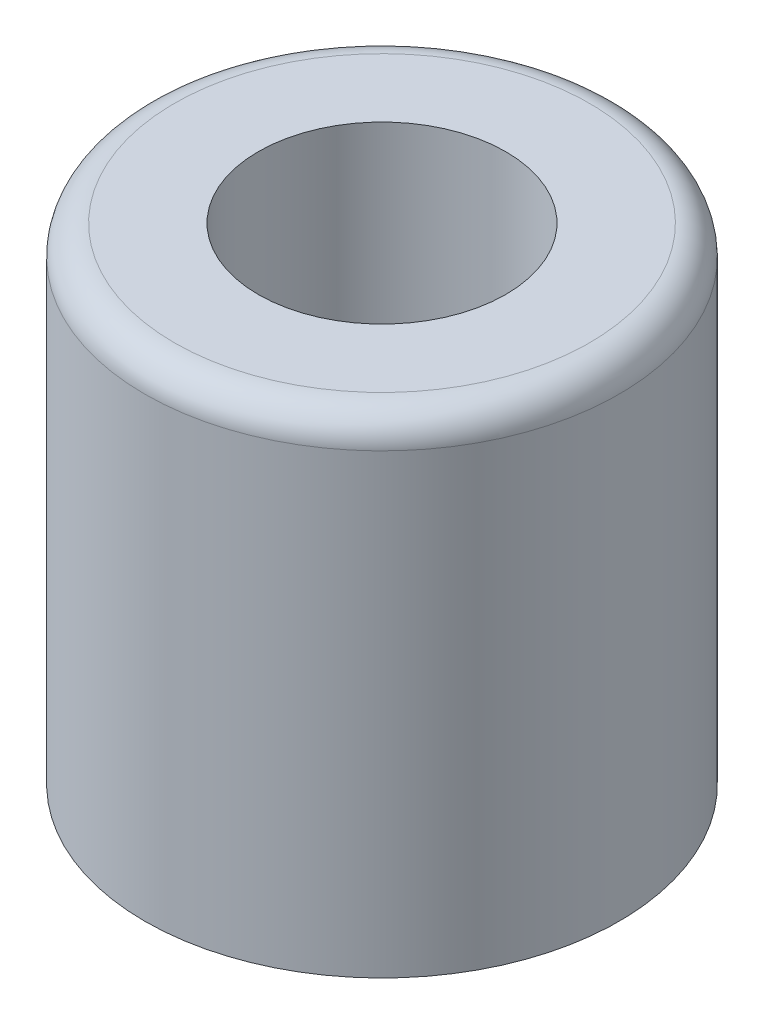
SolidWorks part; units mm, degrees
material "ABS PC"
ref_plane "Front Plane" through (0, 0, 0) normal (0, 0, 1) x (1, 0, 0)
ref_plane "Top Plane" through (0, 0, 0) normal (0, 1, 0) x (1, 0, 0)
ref_plane "Right Plane" through (0, 0, 0) normal (1, 0, 0) x (0, 0, -1)
sketch "Sketch1" plane through (0, 0, 0) normal (0, 1, 0) x (1, 0, 0)
  circle A0 centre (0, 0) radius 4.064
  circle A1 centre (0, 0) radius 2.1209
  dimension "D1" = 8.128
  dimension "D2" = 4.2418
extrude "Extrude1" add sketch "Sketch1" along normal mid plane 8.3312
fillet "Fillet1" radius 0.508 1 edges at (0, 4.1656, 4.064)
ref_axis "Axis1" through (0, -5.3984, 0) along (0, 1, 0)
